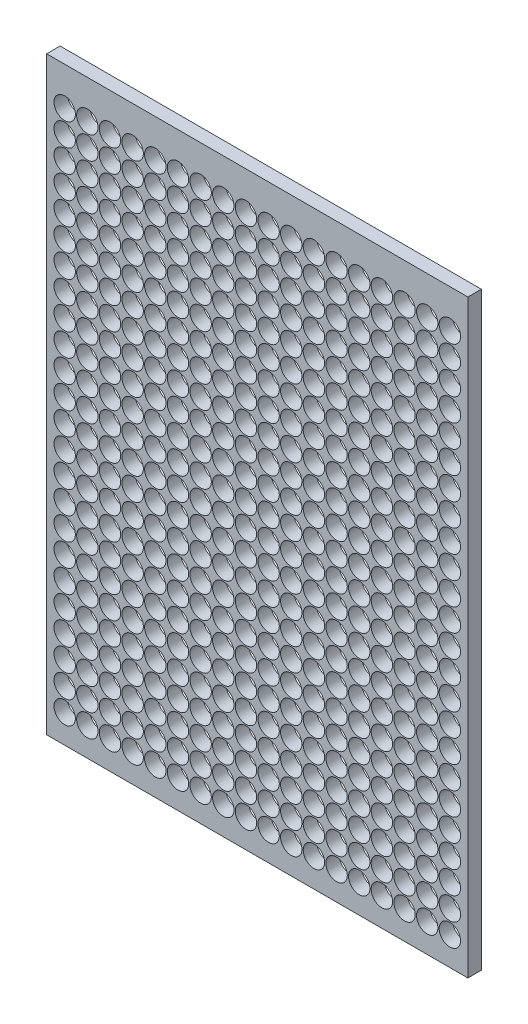
SolidWorks part; units mm, degrees
ref_plane "Ön Düzlem" through (0, 0, 0) normal (0, 0, 1) x (1, 0, 0)
ref_plane "Üst Düzlem" through (0, 0, 0) normal (0, 1, 0) x (1, 0, 0)
ref_plane "Sağ Düzlem" through (0, 0, 0) normal (1, 0, 0) x (0, 0, -1)
sketch "Çizim1" plane through (0, 0, 0) normal (0, 0, 1) x (1, 0, 0)
  line L1 (0, 0) -> (50, 0)
  line L2 (0, 0) -> (0, -70)
  line L3 (0, -70) -> (50, -70)
  line L4 (50, 0) -> (50, -70)
  dimension "D1" = 50
  dimension "D2" = 70
extrude "Yükseklik-Ekstrüzyon1" add sketch "Çizim1" along normal blind 1.6
sketch "Çizim2" plane through (0, 0, 1.6) normal (0, 0, 1) x (1, 0, 0)
  line L1 (0, 0) -> (0, -70) construction
  line L2 (50, 0) -> (0, 0) construction
  line L3 (50, -70) -> (50, 0) construction
  circle A0 centre (2.14, -4.52) radius 1.27
  circle A1 centre (4.8294, -4.52) radius 1.27
  circle A2 centre (7.5188, -4.52) radius 1.27
  circle A3 centre (10.2082, -4.52) radius 1.27
  circle A4 centre (12.8976, -4.52) radius 1.27
  circle A5 centre (15.5871, -4.52) radius 1.27
  circle A6 centre (18.2765, -4.52) radius 1.27
  circle A7 centre (20.9659, -4.52) radius 1.27
  circle A8 centre (23.6553, -4.52) radius 1.27
  circle A9 centre (26.3447, -4.52) radius 1.27
  circle A10 centre (29.0341, -4.52) radius 1.27
  circle A11 centre (31.7235, -4.52) radius 1.27
  circle A12 centre (34.4129, -4.52) radius 1.27
  circle A13 centre (37.1024, -4.52) radius 1.27
  circle A14 centre (39.7918, -4.52) radius 1.27
  circle A15 centre (42.4812, -4.52) radius 1.27
  circle A16 centre (45.1706, -4.52) radius 1.27
  circle A17 centre (47.86, -4.52) radius 1.27
  circle A18 centre (47.86, -7.22) radius 1.27
  circle A19 centre (45.1706, -7.22) radius 1.27
  circle A20 centre (42.4812, -7.22) radius 1.27
  circle A21 centre (39.7918, -7.22) radius 1.27
  circle A22 centre (37.1024, -7.22) radius 1.27
  circle A23 centre (34.4129, -7.22) radius 1.27
  circle A24 centre (31.7235, -7.22) radius 1.27
  circle A25 centre (26.3447, -7.22) radius 1.27
  circle A26 centre (29.0341, -7.22) radius 1.27
  circle A27 centre (23.6553, -7.22) radius 1.27
  circle A28 centre (20.9659, -7.22) radius 1.27
  circle A29 centre (18.2765, -7.22) radius 1.27
  circle A30 centre (15.5871, -7.22) radius 1.27
  circle A31 centre (12.8976, -7.22) radius 1.27
  circle A32 centre (10.2082, -7.22) radius 1.27
  circle A33 centre (7.5188, -7.22) radius 1.27
  circle A34 centre (4.8294, -7.22) radius 1.27
  circle A35 centre (2.14, -7.22) radius 1.27
  circle A36 centre (47.86, -9.92) radius 1.27
  circle A37 centre (45.1706, -9.92) radius 1.27
  circle A38 centre (42.4812, -9.92) radius 1.27
  circle A39 centre (39.7918, -9.92) radius 1.27
  circle A40 centre (37.1024, -9.92) radius 1.27
  circle A41 centre (34.4129, -9.92) radius 1.27
  circle A42 centre (31.7235, -9.92) radius 1.27
  circle A43 centre (26.3447, -9.92) radius 1.27
  circle A44 centre (29.0341, -9.92) radius 1.27
  circle A45 centre (23.6553, -9.92) radius 1.27
  circle A46 centre (20.9659, -9.92) radius 1.27
  circle A47 centre (18.2765, -9.92) radius 1.27
  circle A48 centre (15.5871, -9.92) radius 1.27
  circle A49 centre (12.8976, -9.92) radius 1.27
  circle A50 centre (10.2082, -9.92) radius 1.27
  circle A51 centre (7.5188, -9.92) radius 1.27
  circle A52 centre (4.8294, -9.92) radius 1.27
  circle A53 centre (2.14, -9.92) radius 1.27
  circle A54 centre (47.86, -12.62) radius 1.27
  circle A55 centre (45.1706, -12.62) radius 1.27
  circle A56 centre (42.4812, -12.62) radius 1.27
  circle A57 centre (39.7918, -12.62) radius 1.27
  circle A58 centre (37.1024, -12.62) radius 1.27
  circle A59 centre (34.4129, -12.62) radius 1.27
  circle A60 centre (31.7235, -12.62) radius 1.27
  circle A61 centre (26.3447, -12.62) radius 1.27
  circle A62 centre (29.0341, -12.62) radius 1.27
  circle A63 centre (23.6553, -12.62) radius 1.27
  circle A64 centre (20.9659, -12.62) radius 1.27
  circle A65 centre (18.2765, -12.62) radius 1.27
  circle A66 centre (15.5871, -12.62) radius 1.27
  circle A67 centre (12.8976, -12.62) radius 1.27
  circle A68 centre (10.2082, -12.62) radius 1.27
  circle A69 centre (7.5188, -12.62) radius 1.27
  circle A70 centre (4.8294, -12.62) radius 1.27
  circle A71 centre (2.14, -12.62) radius 1.27
  circle A72 centre (47.86, -15.32) radius 1.27
  circle A73 centre (45.1706, -15.32) radius 1.27
  circle A74 centre (42.4812, -15.32) radius 1.27
  circle A75 centre (39.7918, -15.32) radius 1.27
  circle A76 centre (37.1024, -15.32) radius 1.27
  circle A77 centre (34.4129, -15.32) radius 1.27
  circle A78 centre (31.7235, -15.32) radius 1.27
  circle A79 centre (26.3447, -15.32) radius 1.27
  circle A80 centre (29.0341, -15.32) radius 1.27
  circle A81 centre (23.6553, -15.32) radius 1.27
  circle A82 centre (20.9659, -15.32) radius 1.27
  circle A83 centre (18.2765, -15.32) radius 1.27
  circle A84 centre (15.5871, -15.32) radius 1.27
  circle A85 centre (12.8976, -15.32) radius 1.27
  circle A86 centre (10.2082, -15.32) radius 1.27
  circle A87 centre (7.5188, -15.32) radius 1.27
  circle A88 centre (4.8294, -15.32) radius 1.27
  circle A89 centre (2.14, -15.32) radius 1.27
  circle A90 centre (47.86, -18.02) radius 1.27
  circle A91 centre (45.1706, -18.02) radius 1.27
  circle A92 centre (42.4812, -18.02) radius 1.27
  circle A93 centre (39.7918, -18.02) radius 1.27
  circle A94 centre (37.1024, -18.02) radius 1.27
  circle A95 centre (34.4129, -18.02) radius 1.27
  circle A96 centre (31.7235, -18.02) radius 1.27
  circle A97 centre (26.3447, -18.02) radius 1.27
  circle A98 centre (29.0341, -18.02) radius 1.27
  circle A99 centre (23.6553, -18.02) radius 1.27
  circle A100 centre (20.9659, -18.02) radius 1.27
  circle A101 centre (18.2765, -18.02) radius 1.27
  circle A102 centre (15.5871, -18.02) radius 1.27
  circle A103 centre (12.8976, -18.02) radius 1.27
  circle A104 centre (10.2082, -18.02) radius 1.27
  circle A105 centre (7.5188, -18.02) radius 1.27
  circle A106 centre (4.8294, -18.02) radius 1.27
  circle A107 centre (2.14, -18.02) radius 1.27
  circle A108 centre (47.86, -20.72) radius 1.27
  circle A109 centre (45.1706, -20.72) radius 1.27
  circle A110 centre (42.4812, -20.72) radius 1.27
  circle A111 centre (39.7918, -20.72) radius 1.27
  circle A112 centre (37.1024, -20.72) radius 1.27
  circle A113 centre (34.4129, -20.72) radius 1.27
  circle A114 centre (31.7235, -20.72) radius 1.27
  circle A115 centre (26.3447, -20.72) radius 1.27
  circle A116 centre (29.0341, -20.72) radius 1.27
  circle A117 centre (23.6553, -20.72) radius 1.27
  circle A118 centre (20.9659, -20.72) radius 1.27
  circle A119 centre (18.2765, -20.72) radius 1.27
  circle A120 centre (15.5871, -20.72) radius 1.27
  circle A121 centre (12.8976, -20.72) radius 1.27
  circle A122 centre (10.2082, -20.72) radius 1.27
  circle A123 centre (7.5188, -20.72) radius 1.27
  circle A124 centre (4.8294, -20.72) radius 1.27
  circle A125 centre (2.14, -20.72) radius 1.27
  circle A126 centre (47.86, -23.42) radius 1.27
  circle A127 centre (45.1706, -23.42) radius 1.27
  circle A128 centre (42.4812, -23.42) radius 1.27
  circle A129 centre (39.7918, -23.42) radius 1.27
  circle A130 centre (37.1024, -23.42) radius 1.27
  circle A131 centre (34.4129, -23.42) radius 1.27
  circle A132 centre (31.7235, -23.42) radius 1.27
  circle A133 centre (26.3447, -23.42) radius 1.27
  circle A134 centre (29.0341, -23.42) radius 1.27
  circle A135 centre (23.6553, -23.42) radius 1.27
  circle A136 centre (20.9659, -23.42) radius 1.27
  circle A137 centre (18.2765, -23.42) radius 1.27
  circle A138 centre (15.5871, -23.42) radius 1.27
  circle A139 centre (12.8976, -23.42) radius 1.27
  circle A140 centre (10.2082, -23.42) radius 1.27
  circle A141 centre (7.5188, -23.42) radius 1.27
  circle A142 centre (4.8294, -23.42) radius 1.27
  circle A143 centre (2.14, -23.42) radius 1.27
  circle A144 centre (47.86, -26.12) radius 1.27
  circle A145 centre (45.1706, -26.12) radius 1.27
  circle A146 centre (42.4812, -26.12) radius 1.27
  circle A147 centre (39.7918, -26.12) radius 1.27
  circle A148 centre (37.1024, -26.12) radius 1.27
  circle A149 centre (34.4129, -26.12) radius 1.27
  circle A150 centre (31.7235, -26.12) radius 1.27
  circle A151 centre (26.3447, -26.12) radius 1.27
  circle A152 centre (29.0341, -26.12) radius 1.27
  circle A153 centre (23.6553, -26.12) radius 1.27
  circle A154 centre (20.9659, -26.12) radius 1.27
  circle A155 centre (18.2765, -26.12) radius 1.27
  circle A156 centre (15.5871, -26.12) radius 1.27
  circle A157 centre (12.8976, -26.12) radius 1.27
  circle A158 centre (10.2082, -26.12) radius 1.27
  circle A159 centre (7.5188, -26.12) radius 1.27
  circle A160 centre (4.8294, -26.12) radius 1.27
  circle A161 centre (2.14, -26.12) radius 1.27
  circle A162 centre (47.86, -28.82) radius 1.27
  circle A163 centre (45.1706, -28.82) radius 1.27
  circle A164 centre (42.4812, -28.82) radius 1.27
  circle A165 centre (39.7918, -28.82) radius 1.27
  circle A166 centre (37.1024, -28.82) radius 1.27
  circle A167 centre (34.4129, -28.82) radius 1.27
  circle A168 centre (31.7235, -28.82) radius 1.27
  circle A169 centre (26.3447, -28.82) radius 1.27
  circle A170 centre (29.0341, -28.82) radius 1.27
  circle A171 centre (23.6553, -28.82) radius 1.27
  circle A172 centre (20.9659, -28.82) radius 1.27
  circle A173 centre (18.2765, -28.82) radius 1.27
  circle A174 centre (15.5871, -28.82) radius 1.27
  circle A175 centre (12.8976, -28.82) radius 1.27
  circle A176 centre (10.2082, -28.82) radius 1.27
  circle A177 centre (7.5188, -28.82) radius 1.27
  circle A178 centre (4.8294, -28.82) radius 1.27
  circle A179 centre (2.14, -28.82) radius 1.27
  circle A180 centre (47.86, -31.52) radius 1.27
  circle A181 centre (45.1706, -31.52) radius 1.27
  circle A182 centre (42.4812, -31.52) radius 1.27
  circle A183 centre (39.7918, -31.52) radius 1.27
  circle A184 centre (37.1024, -31.52) radius 1.27
  circle A185 centre (34.4129, -31.52) radius 1.27
  circle A186 centre (31.7235, -31.52) radius 1.27
  circle A187 centre (26.3447, -31.52) radius 1.27
  circle A188 centre (29.0341, -31.52) radius 1.27
  circle A189 centre (23.6553, -31.52) radius 1.27
  circle A190 centre (20.9659, -31.52) radius 1.27
  circle A191 centre (18.2765, -31.52) radius 1.27
  circle A192 centre (15.5871, -31.52) radius 1.27
  circle A193 centre (12.8976, -31.52) radius 1.27
  circle A194 centre (10.2082, -31.52) radius 1.27
  circle A195 centre (7.5188, -31.52) radius 1.27
  circle A196 centre (4.8294, -31.52) radius 1.27
  circle A197 centre (2.14, -31.52) radius 1.27
  circle A198 centre (47.86, -34.22) radius 1.27
  circle A199 centre (45.1706, -34.22) radius 1.27
  circle A200 centre (42.4812, -34.22) radius 1.27
  circle A201 centre (39.7918, -34.22) radius 1.27
  circle A202 centre (37.1024, -34.22) radius 1.27
  circle A203 centre (34.4129, -34.22) radius 1.27
  circle A204 centre (31.7235, -34.22) radius 1.27
  circle A205 centre (26.3447, -34.22) radius 1.27
  circle A206 centre (29.0341, -34.22) radius 1.27
  circle A207 centre (23.6553, -34.22) radius 1.27
  circle A208 centre (20.9659, -34.22) radius 1.27
  circle A209 centre (18.2765, -34.22) radius 1.27
  circle A210 centre (15.5871, -34.22) radius 1.27
  circle A211 centre (12.8976, -34.22) radius 1.27
  circle A212 centre (10.2082, -34.22) radius 1.27
  circle A213 centre (7.5188, -34.22) radius 1.27
  circle A214 centre (4.8294, -34.22) radius 1.27
  circle A215 centre (2.14, -34.22) radius 1.27
  circle A216 centre (47.86, -36.92) radius 1.27
  circle A217 centre (45.1706, -36.92) radius 1.27
  circle A218 centre (42.4812, -36.92) radius 1.27
  circle A219 centre (39.7918, -36.92) radius 1.27
  circle A220 centre (37.1024, -36.92) radius 1.27
  circle A221 centre (34.4129, -36.92) radius 1.27
  circle A222 centre (31.7235, -36.92) radius 1.27
  circle A223 centre (26.3447, -36.92) radius 1.27
  circle A224 centre (29.0341, -36.92) radius 1.27
  circle A225 centre (23.6553, -36.92) radius 1.27
  circle A226 centre (20.9659, -36.92) radius 1.27
  circle A227 centre (18.2765, -36.92) radius 1.27
  circle A228 centre (15.5871, -36.92) radius 1.27
  circle A229 centre (12.8976, -36.92) radius 1.27
  circle A230 centre (10.2082, -36.92) radius 1.27
  circle A231 centre (7.5188, -36.92) radius 1.27
  circle A232 centre (4.8294, -36.92) radius 1.27
  circle A233 centre (2.14, -36.92) radius 1.27
  circle A234 centre (47.86, -39.62) radius 1.27
  circle A235 centre (45.1706, -39.62) radius 1.27
  circle A236 centre (42.4812, -39.62) radius 1.27
  circle A237 centre (39.7918, -39.62) radius 1.27
  circle A238 centre (37.1024, -39.62) radius 1.27
  circle A239 centre (34.4129, -39.62) radius 1.27
  circle A240 centre (31.7235, -39.62) radius 1.27
  circle A241 centre (26.3447, -39.62) radius 1.27
  circle A242 centre (29.0341, -39.62) radius 1.27
  circle A243 centre (23.6553, -39.62) radius 1.27
  circle A244 centre (20.9659, -39.62) radius 1.27
  circle A245 centre (18.2765, -39.62) radius 1.27
  circle A246 centre (15.5871, -39.62) radius 1.27
  circle A247 centre (12.8976, -39.62) radius 1.27
  circle A248 centre (10.2082, -39.62) radius 1.27
  circle A249 centre (7.5188, -39.62) radius 1.27
  circle A250 centre (4.8294, -39.62) radius 1.27
  circle A251 centre (2.14, -39.62) radius 1.27
  circle A252 centre (47.86, -42.32) radius 1.27
  circle A253 centre (45.1706, -42.32) radius 1.27
  circle A254 centre (42.4812, -42.32) radius 1.27
  circle A255 centre (39.7918, -42.32) radius 1.27
  circle A256 centre (37.1024, -42.32) radius 1.27
  circle A257 centre (34.4129, -42.32) radius 1.27
  circle A258 centre (31.7235, -42.32) radius 1.27
  circle A259 centre (26.3447, -42.32) radius 1.27
  circle A260 centre (29.0341, -42.32) radius 1.27
  circle A261 centre (23.6553, -42.32) radius 1.27
  circle A262 centre (20.9659, -42.32) radius 1.27
  circle A263 centre (18.2765, -42.32) radius 1.27
  circle A264 centre (15.5871, -42.32) radius 1.27
  circle A265 centre (12.8976, -42.32) radius 1.27
  circle A266 centre (10.2082, -42.32) radius 1.27
  circle A267 centre (7.5188, -42.32) radius 1.27
  circle A268 centre (4.8294, -42.32) radius 1.27
  circle A269 centre (2.14, -42.32) radius 1.27
  circle A270 centre (47.86, -45.02) radius 1.27
  circle A271 centre (45.1706, -45.02) radius 1.27
  circle A272 centre (42.4812, -45.02) radius 1.27
  circle A273 centre (39.7918, -45.02) radius 1.27
  circle A274 centre (37.1024, -45.02) radius 1.27
  circle A275 centre (34.4129, -45.02) radius 1.27
  circle A276 centre (31.7235, -45.02) radius 1.27
  circle A277 centre (26.3447, -45.02) radius 1.27
  circle A278 centre (29.0341, -45.02) radius 1.27
  circle A279 centre (23.6553, -45.02) radius 1.27
  circle A280 centre (20.9659, -45.02) radius 1.27
  circle A281 centre (18.2765, -45.02) radius 1.27
  circle A282 centre (15.5871, -45.02) radius 1.27
  circle A283 centre (12.8976, -45.02) radius 1.27
  circle A284 centre (10.2082, -45.02) radius 1.27
  circle A285 centre (7.5188, -45.02) radius 1.27
  circle A286 centre (4.8294, -45.02) radius 1.27
  circle A287 centre (2.14, -45.02) radius 1.27
  circle A288 centre (47.86, -47.72) radius 1.27
  circle A289 centre (45.1706, -47.72) radius 1.27
  circle A290 centre (42.4812, -47.72) radius 1.27
  circle A291 centre (39.7918, -47.72) radius 1.27
  circle A292 centre (37.1024, -47.72) radius 1.27
  circle A293 centre (34.4129, -47.72) radius 1.27
  circle A294 centre (31.7235, -47.72) radius 1.27
  circle A295 centre (26.3447, -47.72) radius 1.27
  circle A296 centre (29.0341, -47.72) radius 1.27
  circle A297 centre (23.6553, -47.72) radius 1.27
  circle A298 centre (20.9659, -47.72) radius 1.27
  circle A299 centre (18.2765, -47.72) radius 1.27
  circle A300 centre (15.5871, -47.72) radius 1.27
  circle A301 centre (12.8976, -47.72) radius 1.27
  circle A302 centre (10.2082, -47.72) radius 1.27
  circle A303 centre (7.5188, -47.72) radius 1.27
  circle A304 centre (4.8294, -47.72) radius 1.27
  circle A305 centre (2.14, -47.72) radius 1.27
  circle A306 centre (47.86, -50.42) radius 1.27
  circle A307 centre (45.1706, -50.42) radius 1.27
  circle A308 centre (42.4812, -50.42) radius 1.27
  circle A309 centre (39.7918, -50.42) radius 1.27
  circle A310 centre (37.1024, -50.42) radius 1.27
  circle A311 centre (34.4129, -50.42) radius 1.27
  circle A312 centre (31.7235, -50.42) radius 1.27
  circle A313 centre (26.3447, -50.42) radius 1.27
  circle A314 centre (29.0341, -50.42) radius 1.27
  circle A315 centre (23.6553, -50.42) radius 1.27
  circle A316 centre (20.9659, -50.42) radius 1.27
  circle A317 centre (18.2765, -50.42) radius 1.27
  circle A318 centre (15.5871, -50.42) radius 1.27
  circle A319 centre (12.8976, -50.42) radius 1.27
  circle A320 centre (10.2082, -50.42) radius 1.27
  circle A321 centre (7.5188, -50.42) radius 1.27
  circle A322 centre (4.8294, -50.42) radius 1.27
  circle A323 centre (2.14, -50.42) radius 1.27
  circle A324 centre (47.86, -53.12) radius 1.27
  circle A325 centre (45.1706, -53.12) radius 1.27
  circle A326 centre (42.4812, -53.12) radius 1.27
  circle A327 centre (39.7918, -53.12) radius 1.27
  circle A328 centre (37.1024, -53.12) radius 1.27
  circle A329 centre (34.4129, -53.12) radius 1.27
  circle A330 centre (31.7235, -53.12) radius 1.27
  circle A331 centre (26.3447, -53.12) radius 1.27
  circle A332 centre (29.0341, -53.12) radius 1.27
  circle A333 centre (23.6553, -53.12) radius 1.27
  circle A334 centre (20.9659, -53.12) radius 1.27
  circle A335 centre (18.2765, -53.12) radius 1.27
  circle A336 centre (15.5871, -53.12) radius 1.27
  circle A337 centre (12.8976, -53.12) radius 1.27
  circle A338 centre (10.2082, -53.12) radius 1.27
  circle A339 centre (7.5188, -53.12) radius 1.27
  circle A340 centre (4.8294, -53.12) radius 1.27
  circle A341 centre (2.14, -53.12) radius 1.27
  circle A342 centre (47.86, -55.82) radius 1.27
  circle A343 centre (45.1706, -55.82) radius 1.27
  circle A344 centre (42.4812, -55.82) radius 1.27
  circle A345 centre (39.7918, -55.82) radius 1.27
  circle A346 centre (37.1024, -55.82) radius 1.27
  circle A347 centre (34.4129, -55.82) radius 1.27
  circle A348 centre (31.7235, -55.82) radius 1.27
  circle A349 centre (26.3447, -55.82) radius 1.27
  circle A350 centre (29.0341, -55.82) radius 1.27
  circle A351 centre (23.6553, -55.82) radius 1.27
  circle A352 centre (20.9659, -55.82) radius 1.27
  circle A353 centre (18.2765, -55.82) radius 1.27
  circle A354 centre (15.5871, -55.82) radius 1.27
  circle A355 centre (12.8976, -55.82) radius 1.27
  circle A356 centre (10.2082, -55.82) radius 1.27
  circle A357 centre (7.5188, -55.82) radius 1.27
  circle A358 centre (4.8294, -55.82) radius 1.27
  circle A359 centre (2.14, -55.82) radius 1.27
  circle A360 centre (47.86, -58.52) radius 1.27
  circle A361 centre (45.1706, -58.52) radius 1.27
  circle A362 centre (42.4812, -58.52) radius 1.27
  circle A363 centre (39.7918, -58.52) radius 1.27
  circle A364 centre (37.1024, -58.52) radius 1.27
  circle A365 centre (34.4129, -58.52) radius 1.27
  circle A366 centre (31.7235, -58.52) radius 1.27
  circle A367 centre (26.3447, -58.52) radius 1.27
  circle A368 centre (29.0341, -58.52) radius 1.27
  circle A369 centre (23.6553, -58.52) radius 1.27
  circle A370 centre (20.9659, -58.52) radius 1.27
  circle A371 centre (18.2765, -58.52) radius 1.27
  circle A372 centre (15.5871, -58.52) radius 1.27
  circle A373 centre (12.8976, -58.52) radius 1.27
  circle A374 centre (10.2082, -58.52) radius 1.27
  circle A375 centre (7.5188, -58.52) radius 1.27
  circle A376 centre (4.8294, -58.52) radius 1.27
  circle A377 centre (2.14, -58.52) radius 1.27
  circle A378 centre (47.86, -61.22) radius 1.27
  circle A379 centre (45.1706, -61.22) radius 1.27
  circle A380 centre (42.4812, -61.22) radius 1.27
  circle A381 centre (39.7918, -61.22) radius 1.27
  circle A382 centre (37.1024, -61.22) radius 1.27
  circle A383 centre (34.4129, -61.22) radius 1.27
  circle A384 centre (31.7235, -61.22) radius 1.27
  circle A385 centre (26.3447, -61.22) radius 1.27
  circle A386 centre (29.0341, -61.22) radius 1.27
  circle A387 centre (23.6553, -61.22) radius 1.27
  circle A388 centre (20.9659, -61.22) radius 1.27
  circle A389 centre (18.2765, -61.22) radius 1.27
  circle A390 centre (15.5871, -61.22) radius 1.27
  circle A391 centre (12.8976, -61.22) radius 1.27
  circle A392 centre (10.2082, -61.22) radius 1.27
  circle A393 centre (7.5188, -61.22) radius 1.27
  circle A394 centre (4.8294, -61.22) radius 1.27
  circle A395 centre (2.14, -61.22) radius 1.27
  circle A396 centre (47.86, -63.92) radius 1.27
  circle A397 centre (45.1706, -63.92) radius 1.27
  circle A398 centre (42.4812, -63.92) radius 1.27
  circle A399 centre (39.7918, -63.92) radius 1.27
  circle A400 centre (37.1024, -63.92) radius 1.27
  circle A401 centre (34.4129, -63.92) radius 1.27
  circle A402 centre (31.7235, -63.92) radius 1.27
  circle A403 centre (26.3447, -63.92) radius 1.27
  circle A404 centre (29.0341, -63.92) radius 1.27
  circle A405 centre (23.6553, -63.92) radius 1.27
  circle A406 centre (20.9659, -63.92) radius 1.27
  circle A407 centre (18.2765, -63.92) radius 1.27
  circle A408 centre (15.5871, -63.92) radius 1.27
  circle A409 centre (12.8976, -63.92) radius 1.27
  circle A410 centre (10.2082, -63.92) radius 1.27
  circle A411 centre (7.5188, -63.92) radius 1.27
  circle A412 centre (4.8294, -63.92) radius 1.27
  circle A413 centre (2.14, -63.92) radius 1.27
  circle A414 centre (47.86, -66.62) radius 1.27
  circle A415 centre (45.1706, -66.62) radius 1.27
  circle A416 centre (42.4812, -66.62) radius 1.27
  circle A417 centre (39.7918, -66.62) radius 1.27
  circle A418 centre (37.1024, -66.62) radius 1.27
  circle A419 centre (34.4129, -66.62) radius 1.27
  circle A420 centre (31.7235, -66.62) radius 1.27
  circle A421 centre (26.3447, -66.62) radius 1.27
  circle A422 centre (29.0341, -66.62) radius 1.27
  circle A423 centre (23.6553, -66.62) radius 1.27
  circle A424 centre (20.9659, -66.62) radius 1.27
  circle A425 centre (18.2765, -66.62) radius 1.27
  circle A426 centre (15.5871, -66.62) radius 1.27
  circle A427 centre (12.8976, -66.62) radius 1.27
  circle A428 centre (10.2082, -66.62) radius 1.27
  circle A429 centre (7.5188, -66.62) radius 1.27
  circle A430 centre (4.8294, -66.62) radius 1.27
  circle A431 centre (2.14, -66.62) radius 1.27
  dimension "D1" = 2.54
  dimension "D2" = 2.14
  dimension "D3" = 4.52
  dimension "D5" = 2.14
  dimension "D4" = 18
  dimension "D6" = 24
extrude "Kes-Ekstrüzyon1" cut sketch "Çizim2" against normal blind 1.6
